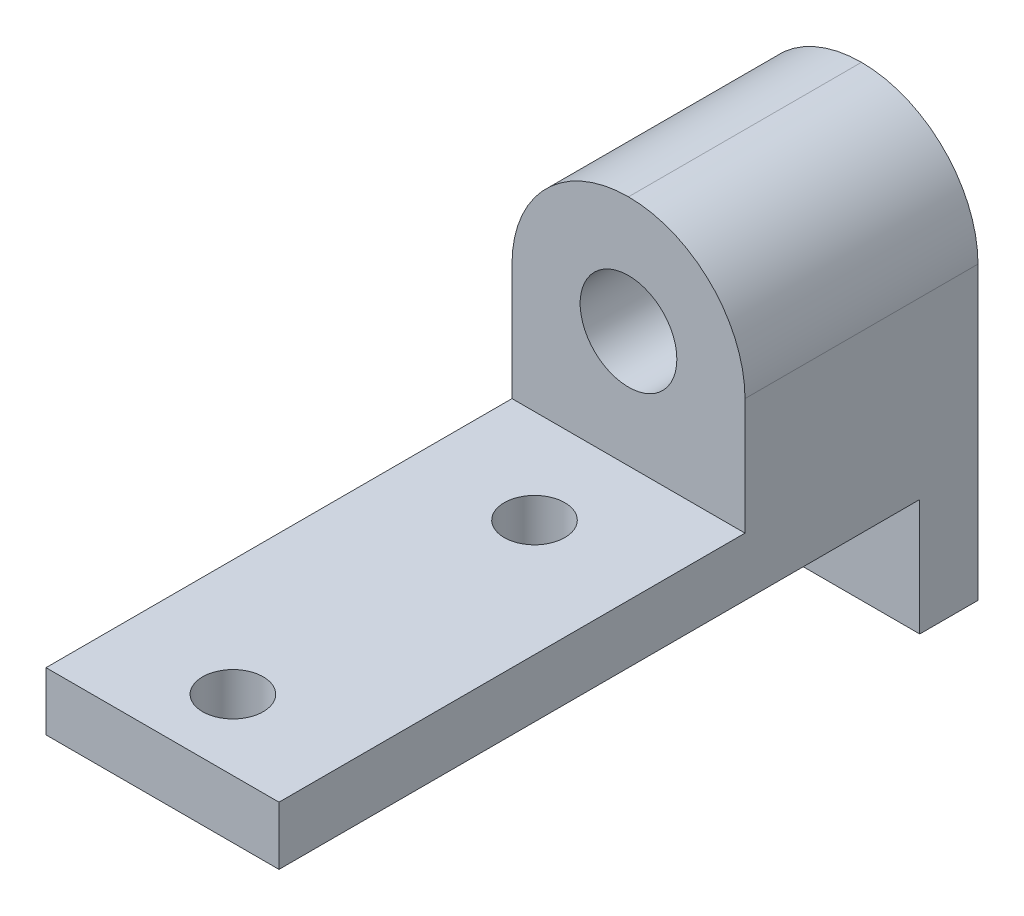
SolidWorks part; units mm, degrees
ref_plane "前视基准面" through (0, 0, 0) normal (0, 0, 1) x (1, 0, 0)
ref_plane "上视基准面" through (0, 0, 0) normal (0, 1, 0) x (1, 0, 0)
ref_plane "右视基准面" through (0, 0, 0) normal (1, 0, 0) x (0, 0, -1)
sketch "草图1" plane through (0, 0, 0) normal (0, 1, 0) x (1, 0, 0)
  line L1 (-7.3659, -8.1541) -> (12.6341, -8.1541)
  line L2 (-7.3659, -8.1541) -> (-7.3659, -48.1541)
  line L3 (-7.3659, -48.1541) -> (12.6341, -48.1541)
  line L4 (12.6341, -8.1541) -> (12.6341, -48.1541)
  dimension "D1" = 20
  dimension "D2" = 40
extrude "凸台-拉伸1" add sketch "草图1" along normal blind 5
sketch "草图2" plane through (0, 5, 0) normal (0, 1, 0) x (1, 0, 0)
  line L0 (-7.3659, -8.1541) -> (-7.3659, -48.1541) construction
  line L1 (-7.3659, -18.1541) -> (12.6341, -18.1541)
  line L2 (-7.3659, -18.1541) -> (-7.3659, -38.1541)
  line L3 (-7.3659, -38.1541) -> (12.6341, -38.1541)
  line L4 (12.6341, -18.1541) -> (12.6341, -38.1541)
  line L5 (12.6341, -48.1541) -> (12.6341, -8.1541) construction
  line L6 (12.6341, -8.1541) -> (-7.3659, -8.1541) construction
  line L7 (-7.3659, -48.1541) -> (12.6341, -48.1541) construction
  dimension "D1" = 10
  dimension "D2" = 10
extrude "凸台-拉伸2" add sketch "草图2" along normal blind 20
sketch "草图3" plane through (0, 0, 38.1541) normal (0, 0, 1) x (1, 0, 0)
  circle A0 centre (2.6341, 15) radius 4.15
  dimension "D1" = 8.3
extrude "切除-拉伸1" cut sketch "草图3" against normal through all
fillet "圆角1" radius 10 2 edges at (12.6341, 25, 28.1541) (-7.3659, 25, 28.1541)
sketch "草图6" plane through (0, 5, 0) normal (0, 1, 0) x (1, 0, 0)
  line L1 (-7.3659, -18.1541) -> (12.6341, -18.1541)
  line L2 (-7.3659, -18.1541) -> (-7.3659, 7.6374)
  line L3 (-7.3659, 7.6374) -> (12.6341, 7.6374)
  line L4 (12.6341, -18.1541) -> (12.6341, 7.6374)
extrude "切除-拉伸3" cut sketch "草图6" against normal through all
sketch "草图7" plane through (0, 0, 0) normal (0, -1, 0) x (1, 0, 0)
  line L0 (12.6341, 48.1541) -> (12.6341, 18.1541) construction
  line L5 (-7.3659, 18.1541) -> (12.6341, 18.1541)
  line L6 (-7.3659, 18.1541) -> (-7.3659, 23.1541)
  line L7 (-7.3659, 23.1541) -> (12.6341, 23.1541)
  line L8 (12.6341, 18.1541) -> (12.6341, 23.1541)
  dimension "D1" = 5
extrude "凸台-拉伸5" add sketch "草图7" along normal blind 10
sketch "草图8" plane through (0, 0, 48.1541) normal (0, 0, 1) x (1, 0, 0)
  line L4 (-7.3659, 0) -> (12.6341, 0)
  line L5 (12.6341, 0) -> (12.6341, 5)
  line L6 (12.6341, 5) -> (-7.3659, 5)
  line L7 (-7.3659, 5) -> (-7.3659, 0)
  line L8 (-7.3659, 0) -> (12.6341, 0)
  line L9 (12.6341, 0) -> (12.6341, 5)
  line L10 (12.6341, 5) -> (-7.3659, 5)
  line L11 (-7.3659, 5) -> (-7.3659, 0)
  dimension "D1" = 0
extrude "凸台-拉伸6" add sketch "草图8" along normal blind 10
sketch "草图10" plane through (0, 0, 23.1541) normal (0, 0, 1) x (1, 0, 0)
  line L0 (12.6341, -10) -> (-7.3659, -10) construction
  circle A0 centre (2.6341, -5) radius 1.6
  dimension "D1" = 3.2
  dimension "D2" = 5
extrude "切除-拉伸5" cut sketch "草图10" against normal through all
sketch "草图11" plane through (0, 0, 58.1541) normal (0, 0, 1) x (1, 0, 0)
  line L4 (-7.3659, 5) -> (-7.3659, 0)
  line L5 (-7.3659, 0) -> (12.6341, 0)
  line L6 (12.6341, 0) -> (12.6341, 5)
  line L7 (12.6341, 5) -> (-7.3659, 5)
  line L8 (-7.3659, 5) -> (-7.3659, 0)
  line L9 (-7.3659, 0) -> (12.6341, 0)
  line L10 (12.6341, 0) -> (12.6341, 5)
  line L11 (12.6341, 5) -> (-7.3659, 5)
  dimension "D1" = 0
extrude "凸台-拉伸7" add sketch "草图11" along normal blind 20
sketch "草图12" plane through (0, 5, 0) normal (0, 1, 0) x (1, 0, 0)
  circle A0 centre (2.6341, -46.2217) radius 2.6
  circle A1 centre (2.6341, -72.1102) radius 2.6
  dimension "D1" = 5.2
  dimension "D2" = 5.2
extrude "切除-拉伸7" cut sketch "草图12" against normal through all
